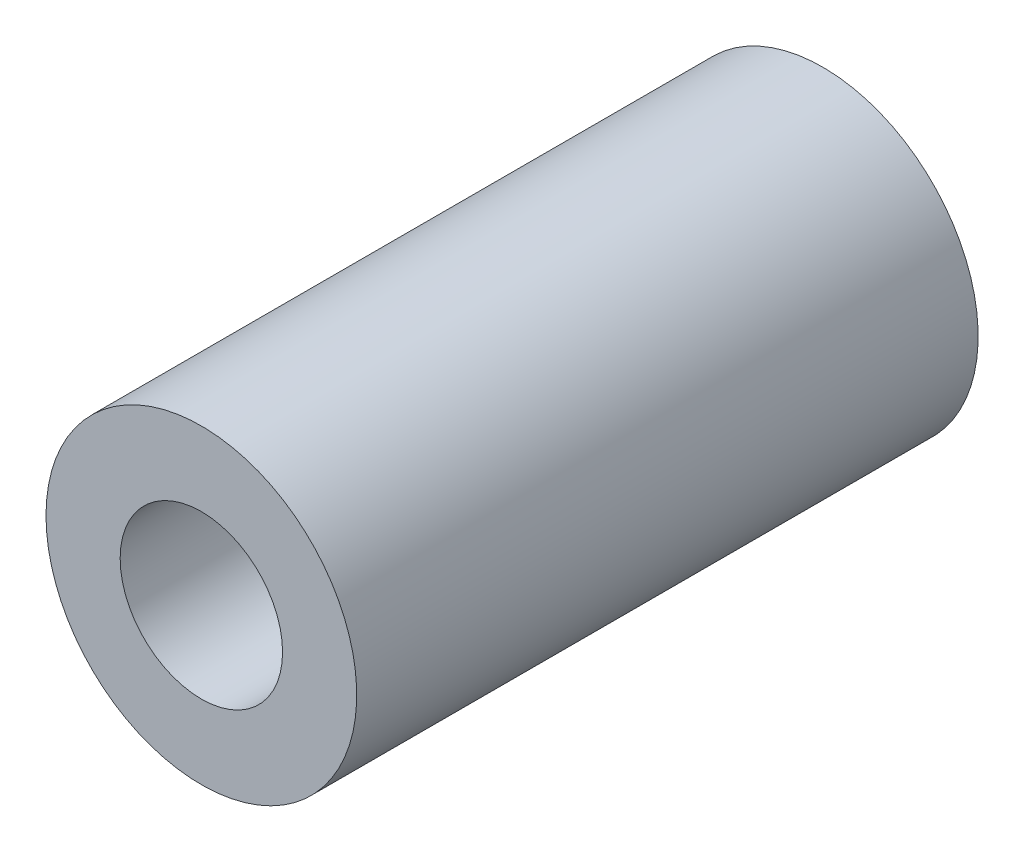
SolidWorks part; units mm, degrees
material "6061-T6 (SS)"
ref_plane "Front Plane" through (0, 0, 0) normal (0, 0, 1) x (1, 0, 0)
ref_plane "Top Plane" through (0, 0, 0) normal (0, 1, 0) x (1, 0, 0)
ref_plane "Right Plane" through (0, 0, 0) normal (1, 0, 0) x (0, 0, -1)
sketch "Sketch1" plane through (0, 0, 0) normal (0, 0, 1) x (1, 0, 0)
  circle A0 centre (0, 0) radius 4.7625
  circle A1 centre (0, 0) radius 2.4892
  dimension "D1" = 4.9784
  dimension "D2" = 9.525
extrude "Boss-Extrude1" add sketch "Sketch1" along normal blind 19.05
